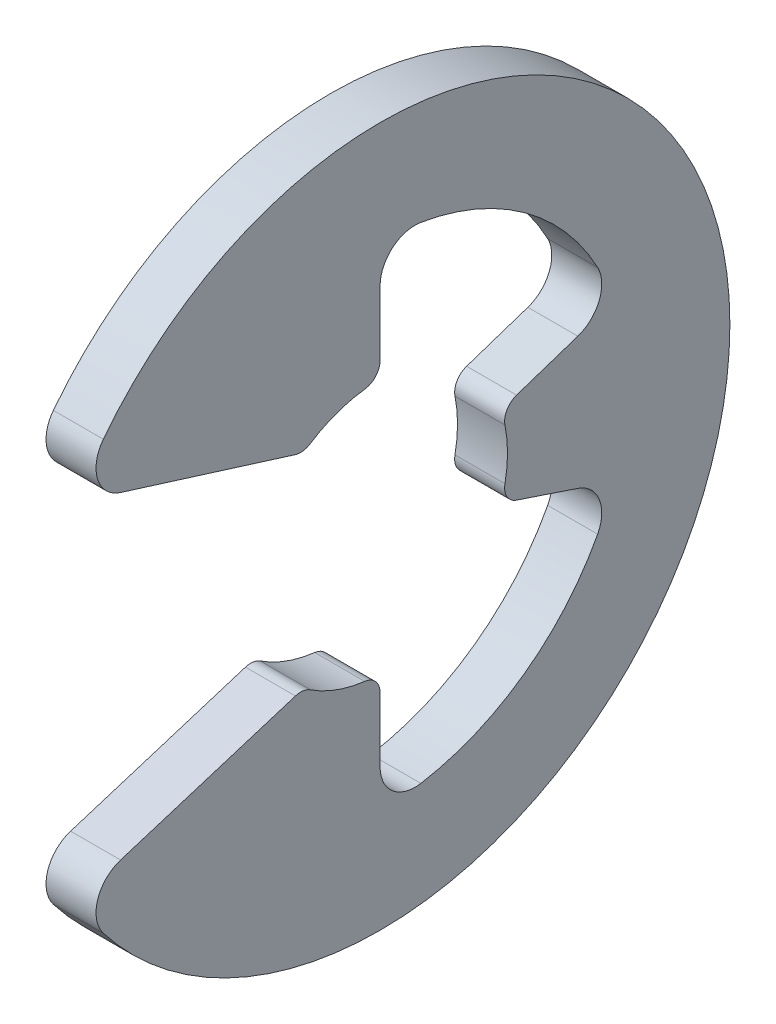
SolidWorks part; units mm, degrees
ref_plane "Front" through (0, 0, 0) normal (0, 0, 1) x (1, 0, 0)
ref_plane "Top" through (0, 0, 0) normal (0, 1, 0) x (1, 0, 0)
ref_plane "Right" through (0, 0, 0) normal (1, 0, 0) x (0, 0, -1)
sketch "Sketch1" plane through (0, 0, 0) normal (1, 0, 0) x (0, 0, -1)
  line L0 (-1.5453, -0.8795) -> (-0.3886, -0.5182)
  line L1 (-1.5453, 0.8795) -> (-0.3886, 0.5182)
  line L2 (0, -0.6477) -> (0, -1.252)
  line L3 (0, 0.6477) -> (0, 1.252)
  line L4 (0.6145, -0.2048) -> (1.1877, -0.3959)
  line L5 (0.6145, 0.2048) -> (1.1877, 0.3959)
  line L6 (0, 0) -> (-0.6477, 0) construction
  line L7 (0.6145, 0.2048) -> (0.6145, -0.2048) construction
  line L8 (0, -0.6477) -> (-0.3886, -0.5182) construction
  line L9 (0, 1.778) -> (0, -1.778) construction
  circle A2 centre (0, 0) radius 0.6477 construction
  arc A3 (-1.5453, -0.8795) -> (-1.5453, 0.8795) centre (0, 0) ccw
  arc A4 (-0.3886, -0.5182) -> (0, -0.6477) centre (0, 0) ccw
  arc A5 (-0.3886, 0.5182) -> (0, 0.6477) centre (0, 0) cw
  arc A6 (0.6145, 0.2048) -> (0.6145, -0.2048) centre (0, 0) cw
  arc A7 (0, -1.252) -> (1.1877, -0.3959) centre (0, 0) ccw
  arc A8 (1.1877, 0.3959) -> (0, 1.252) centre (0, 0) ccw
  point P8 (0, 0.6477)
  point P12 (0, 1.778)
  dimension "Free Diameter" = 1.2954
  dimension "D1" = 1.252
  dimension "Ring OD" = 3.556
  dimension "D2" = 0.7574
  dimension "D10" = 1.0363
sketch "Sketch4" plane through (0, 0, 0) normal (0, 0, 1) x (1, 0, 0)
  line L0 (-0.127, 1.778) -> (0.127, 1.778) construction
  point P3 (0, 1.778)
  dimension "Ring Thickness" = 0.254
sketch "Sketch3" plane through (0, 0, 0) normal (1, 0, 0) x (0, 0, -1)
  line L6 (0.6145, -0.2048) -> (1.1877, -0.3959)
  line L7 (0, -1.252) -> (0, -0.6477)
  line L8 (-0.3886, -0.5182) -> (-1.5453, -0.8795)
  line L9 (-1.5453, 0.8795) -> (-0.3886, 0.5182)
  line L10 (0, 0.6477) -> (0, 1.252)
  line L11 (1.1877, 0.3959) -> (0.6145, 0.2048)
  line L12 (0.6145, -0.2048) -> (1.1877, -0.3959)
  line L13 (0, -1.252) -> (0, -0.6477)
  line L14 (-0.3886, -0.5182) -> (-1.5453, -0.8795)
  line L15 (-1.5453, 0.8795) -> (-0.3886, 0.5182)
  line L16 (0, 0.6477) -> (0, 1.252)
  line L17 (1.1877, 0.3959) -> (0.6145, 0.2048)
  arc A6 (0, -1.252) -> (1.1877, -0.3959) centre (0, 0) ccw
  arc A7 (-0.3886, -0.5182) -> (0, -0.6477) centre (0, 0) ccw
  arc A8 (-1.5453, -0.8795) -> (-1.5453, 0.8795) centre (0, 0) ccw
  arc A9 (0, 0.6477) -> (-0.3886, 0.5182) centre (0, 0) ccw
  arc A10 (1.1877, 0.3959) -> (0, 1.252) centre (0, 0) ccw
  arc A11 (0.6145, -0.2048) -> (0.6145, 0.2048) centre (0, 0) ccw
  arc A12 (0, -1.252) -> (1.1877, -0.3959) centre (0, 0) ccw
  arc A13 (-0.3886, -0.5182) -> (0, -0.6477) centre (0, 0) ccw
  arc A14 (-1.5453, -0.8795) -> (-1.5453, 0.8795) centre (0, 0) ccw
  arc A15 (0, 0.6477) -> (-0.3886, 0.5182) centre (0, 0) ccw
  arc A16 (1.1877, 0.3959) -> (0, 1.252) centre (0, 0) ccw
  arc A17 (0.6145, -0.2048) -> (0.6145, 0.2048) centre (0, 0) ccw
  dimension "D1" = 0
extrude "Boss-Extrude1" add sketch "Sketch3" along normal up to vertex (0.127 mm away) and the other way up to vertex (0.127 mm away) up to point (0.127, 1.778, 0) other way up to point (-0.127, 1.778, 0)
fillet "Fillet1" radius 0.1778 6 edges at (0, -1.252, 0) (0, -0.3959, -1.1877) (0, 0.3959, -1.1877) (0, 1.252, 0) (0, -0.8795, 1.5453) (0, 0.8795, 1.5453)
fillet "Fillet2" radius 0.0889 6 edges at (0, -0.6477, 0) (0, -0.5182, 0.3886) (0, 0.2048, -0.6145) (0, -0.2048, -0.6145) (0, 0.5182, 0.3886) (0, 0.6477, 0)
equation "\"D1@Sketch1\" =  ( \"Ring OD@Sketch1\" + \"Free Diameter@Sketch1\" )  / 3.875"
equation "\"D10@Sketch1\"=\"Free Diameter@Sketch1\" * .8"
equation "\"D1@Fillet1\"=\"Ring Thickness@Sketch4\"*.7"
equation "\"D1@Fillet2\"=\"D1@Fillet1\"/2"
